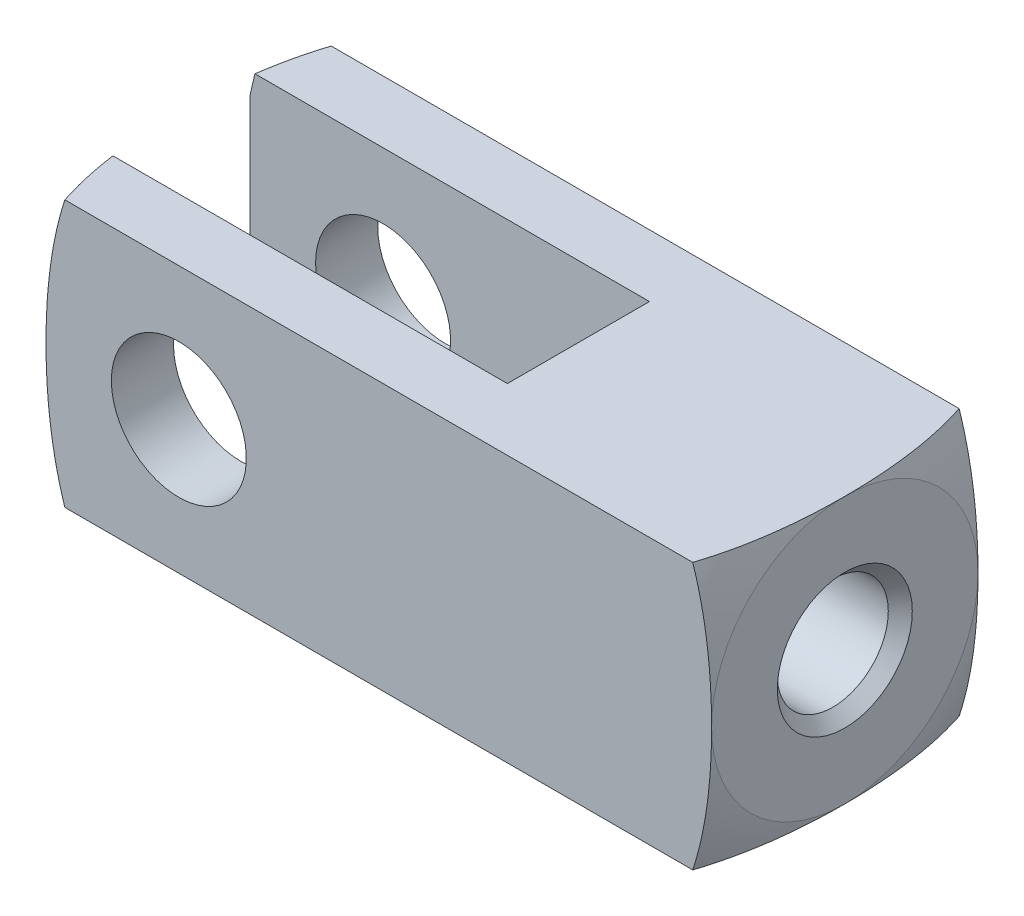
SolidWorks part; units mm, degrees
material "Plain Carbon Steel"
ref_plane "Front Plane" through (0, 0, 0) normal (0, 0, 1) x (1, 0, 0)
ref_plane "Top Plane" through (0, 0, 0) normal (0, 1, 0) x (1, 0, 0)
ref_plane "Right Plane" through (0, 0, 0) normal (1, 0, 0) x (0, 0, -1)
sketch "Sketch1" plane through (0, 0, 0) normal (0, 0, 1) x (1, 0, 0)
  line L0 (-4.7498, 4.7625) -> (-4.7498, -4.7625)
  line L1 (-4.7498, -4.7625) -> (19.05, -4.7625)
  line L2 (19.05, -4.7625) -> (19.05, 4.7625)
  line L3 (19.05, 4.7625) -> (-4.7498, 4.7625)
extrude "Boss-Extrude1" add sketch "Sketch1" against normal blind 4.7625 and the other way blind 4.7625
sketch "Sketch2" plane through (0, 0, 0) normal (0, 1, 0) x (1, 0, 0)
  line L0 (-4.7498, 2.54) -> (-4.7498, -2.54)
  line L1 (-4.7498, -2.54) -> (9.525, -2.54)
  line L2 (9.525, -2.54) -> (9.525, 2.54)
  line L3 (9.525, 2.54) -> (-4.7498, 2.54)
extrude "Cut-Extrude1" cut sketch "Sketch2" along normal blind 4.7625 and the other way blind 4.7625
hole_wizard "Hole1" positions "Sketch4" profile "Sketch3" legacy
sketch "Sketch4" plane through (19.05, 0, 0) normal (1, 0, 0) x (0, 0, -1)
  point P0 (0, 0)
sketch "Sketch3" plane through (19.05, 0, 0) normal (0, 1, 0) x (0, 0, -1)
  line L0 (0, 0) -> (0, 7.874)
  line L1 (0, 7.874) -> (1.9837, 7.874)
  line L2 (1.9837, 7.874) -> (1.9837, 0.4293)
  line L3 (1.9837, 0.4293) -> (2.413, 0)
  line L4 (2.413, 0) -> (0, 0)
  line L5 (0, -6.4453) -> (0, 115.525) construction
  line L6 (-1.9837, 0.4293) -> (-2.413, 0) construction
  dimension "Diameter" = 3.9675
  dimension "Depth" = 7.874
  dimension "C-Sink Angle" = 90
  dimension "C-Sink Diameter" = 4.826
cosmetic thread "Cosmetic Thread1" parameters "D1"=7.874, "D2"=4.826
ref_plane "Plane1" through (0, 0, 6.35) normal (0, 0, 1) x (1, 0, 0)
ref_plane "Plane2" through (0, 0, -6.35) normal (0, 0, 1) x (1, 0, 0)
ref_plane "Plane3" through (23.876, 0, 0) normal (1, 0, 0) x (0, 0, -1)
hole_wizard "Hole2" positions "Sketch6" profile "Sketch5" legacy
sketch "Sketch6" plane through (11.176, 0, 0) normal (1, 0, 0) x (0, 0, -1)
  point P0 (0, 0)
sketch "Sketch5" plane through (11.176, 0, 0) normal (0, 1, 0) x (0, 0, -1)
  line L0 (0, 0) -> (0, 1.651)
  line L1 (0, 1.651) -> (1.9837, 1.651)
  line L2 (1.9837, 1.651) -> (1.9837, 0)
  line L3 (1.9837, 0) -> (0, 0)
  line L4 (0, 110) -> (0, -10) construction
  dimension "Diameter" = 3.9675
  dimension "Depth" = 1.651
hole_wizard "Hole3" positions "Sketch8" profile "Sketch7" legacy
sketch "Sketch8" plane through (0, 0, -4.7625) normal (0, 0, -1) x (-1, 0, 0)
  point P0 (0, 0)
sketch "Sketch7" plane through (0, 0, -4.7625) normal (1, 0, 0) x (0, 1, 0)
  line L0 (0, 0) -> (0, 9.525)
  line L1 (0, 9.525) -> (2.413, 9.525)
  line L2 (2.413, 9.525) -> (2.413, 0)
  line L3 (2.413, 0) -> (0, 0)
  line L4 (0, 110) -> (0, -10) construction
  dimension "Diameter" = 4.826
  dimension "Depth" = 9.525
sketch "Sketch9" plane through (0, 0, 0) normal (0, 0, 1) x (1, 0, 0)
  line L0 (19.05, 0) -> (19.05, 4.7625)
  line L1 (16.51, 9.525) -> (23.8125, 9.525)
  line L2 (23.8125, 9.525) -> (23.8125, 0)
  line L3 (23.8125, 0) -> (19.05, 0)
  line L4 (23.8125, 0) -> (19.05, 0) construction
  arc A0 (19.05, 4.7625) -> (16.51, 9.525) centre (8.8503, 2.3812) ccw
revolve "Cut-Revolve1" cut sketch "Sketch9" angle 360 about L4 reverse direction yes
sketch "Sketch10" plane through (0, 0, 0) normal (0, 0, 1) x (1, 0, 0)
  line L0 (-9.5123, 0) -> (-9.5123, 9.525)
  line L1 (-9.5123, 9.525) -> (-2.2098, 9.525)
  line L2 (-4.7498, 4.7625) -> (-4.7498, 0)
  line L3 (-4.7498, 0) -> (-9.5123, 0)
  line L4 (-4.7498, 0) -> (-9.5123, 0) construction
  arc A0 (-2.2098, 9.525) -> (-4.7498, 4.7625) centre (5.4499, 2.3813) ccw
revolve "Cut-Revolve2" cut sketch "Sketch10" angle 360 about L4 reverse direction yes
ref_plane "Plane4" through (19.05, 0, 0) normal (1, 0, 0) x (0, 0, -1)
ref_plane "Plane5" through (9.525, 0, 0) normal (1, 0, 0) x (0, 0, -1)
ref_plane "dummy XY" through (0, 0, 0) normal (0, 0, 1) x (1, 0, 0)
ref_plane "dummy XZ" through (0, 0, 0) normal (0, -1, 0) x (-1, 0, 0)
ref_plane "dummy YZ" through (0, 0, 0) normal (1, 0, 0) x (0, 0, -1)
ref_axis "dummy X" through (-80.9, 0, 0) along (1, 0, 0)
ref_axis "dummy Y" through (0, -50, 0) along (0, 1, 0)
ref_axis "dummy Z" through (0, 0, 80.9) along (0, 0, -1)
sketch3d "dummy"
  point P0 (0, 0, 0)
ref_plane "h1 XY" through (0, 0, 0) normal (0, 0, 1) x (1, 0, 0)
ref_plane "h1 XZ" through (0, 4.7625, 0) normal (0, -1, 0) x (-1, 0, 0)
ref_plane "h1 YZ" through (-4.7498, 0, 0) normal (1, 0, 0) x (0, 0, -1)
ref_axis "h1 X" through (-80.9, 4.7625, 0) along (1, 0, 0)
ref_axis "h1 Y" through (-4.7498, -50, 0) along (0, 1, 0)
ref_axis "h1 Z" through (-4.7498, 4.7625, 80.9) along (0, 0, -1)
sketch3d "h1"
  point P0 (-4.7498, 4.7625, 0)
ref_plane "h2 XY" through (0, 0, 0) normal (0, 0, 1) x (1, 0, 0)
ref_plane "h2 XZ" through (0, -4.7625, 0) normal (0, -1, 0) x (-1, 0, 0)
ref_plane "h2 YZ" through (-4.7498, 0, 0) normal (1, 0, 0) x (0, 0, -1)
ref_axis "h2 X" through (-80.9, -4.7625, 0) along (1, 0, 0)
ref_axis "h2 Y" through (-4.7498, -50, 0) along (0, 1, 0)
ref_axis "h2 Z" through (-4.7498, -4.7625, 80.9) along (0, 0, -1)
sketch3d "h2"
  point P0 (-4.7498, -4.7625, 0)
ref_plane "l1 XY" through (0, 0, 0) normal (0, 0, 1) x (1, 0, 0)
ref_plane "l1 XZ" through (0, 4.7625, 0) normal (0, -1, 0) x (-1, 0, 0)
ref_plane "l1 YZ" through (19.05, 0, 0) normal (1, 0, 0) x (0, 0, -1)
ref_axis "l1 X" through (-80.9, 4.7625, 0) along (1, 0, 0)
ref_axis "l1 Y" through (19.05, -50, 0) along (0, 1, 0)
ref_axis "l1 Z" through (19.05, 4.7625, 80.9) along (0, 0, -1)
sketch3d "l1"
  point P0 (19.05, 4.7625, 0)
ref_plane "l11 XY" through (0, 0, 0) normal (0, 0, 1) x (1, 0, 0)
ref_plane "l11 XZ" through (0, 4.7625, 0) normal (0, -1, 0) x (-1, 0, 0)
ref_plane "l11 YZ" through (19.05, 0, 0) normal (1, 0, 0) x (0, 0, -1)
ref_axis "l11 X" through (-80.9, 4.7625, 0) along (1, 0, 0)
ref_axis "l11 Y" through (19.05, -50, 0) along (0, 1, 0)
ref_axis "l11 Z" through (19.05, 4.7625, 80.9) along (0, 0, -1)
sketch3d "l11"
  point P0 (19.05, 4.7625, 0)
ref_plane "l12 XY" through (0, 0, 0) normal (0, 0, 1) x (1, 0, 0)
ref_plane "l12 XZ" through (0, 4.7625, 0) normal (0, -1, 0) x (-1, 0, 0)
ref_plane "l12 YZ" through (0, 0, 0) normal (1, 0, 0) x (0, 0, -1)
ref_axis "l12 X" through (-80.9, 4.7625, 0) along (1, 0, 0)
ref_axis "l12 Y" through (0, -50, 0) along (0, 1, 0)
ref_axis "l12 Z" through (0, 4.7625, 80.9) along (0, 0, -1)
sketch3d "l12"
  point P0 (0, 4.7625, 0)
ref_plane "l2 XY" through (0, 0, 0) normal (0, 0, 1) x (1, 0, 0)
ref_plane "l2 XZ" through (0, 4.7625, 0) normal (0, -1, 0) x (-1, 0, 0)
ref_plane "l2 YZ" through (-4.7498, 0, 0) normal (1, 0, 0) x (0, 0, -1)
ref_axis "l2 X" through (-80.9, 4.7625, 0) along (1, 0, 0)
ref_axis "l2 Y" through (-4.7498, -50, 0) along (0, 1, 0)
ref_axis "l2 Z" through (-4.7498, 4.7625, 80.9) along (0, 0, -1)
sketch3d "l2"
  point P0 (-4.7498, 4.7625, 0)
ref_plane "l21 XY" through (0, 0, 0) normal (0, 1, 0) x (1, 0, 0)
ref_plane "l21 XZ" through (0, 0, 0) normal (0, 0, 1) x (1, 0, 0)
ref_plane "l21 YZ" through (19.05, 0, 0) normal (1, 0, 0) x (0, 0, -1)
ref_axis "l21 X" through (-80.9, 0, 0) along (1, 0, 0)
ref_axis "l21 Y" through (19.05, 0, 50) along (0, 0, -1)
ref_axis "l21 Z" through (19.05, 50, 0) along (0, -1, 0)
sketch3d "l21"
  point P0 (19.05, 0, 0)
ref_plane "l22 XY" through (0, 0, 0) normal (0, 1, 0) x (1, 0, 0)
ref_plane "l22 XZ" through (0, 0, 0) normal (0, 0, 1) x (1, 0, 0)
ref_plane "l22 YZ" through (9.525, 0, 0) normal (1, 0, 0) x (0, 0, -1)
ref_axis "l22 X" through (-80.9, 0, 0) along (1, 0, 0)
ref_axis "l22 Y" through (9.525, 0, 50) along (0, 0, -1)
ref_axis "l22 Z" through (9.525, 50, 0) along (0, -1, 0)
sketch3d "l22"
  point P0 (9.525, 0, 0)
ref_plane "piston_rod_clevis XY" through (19.05, 0, 0) normal (1, 0, 0) x (0, 0, -1)
ref_plane "piston_rod_clevis XZ" through (0, 0, 0) normal (0, -1, 0) x (-1, 0, 0)
ref_plane "piston_rod_clevis YZ" through (0, 0, 0) normal (0, 0, -1) x (-1, 0, 0)
ref_axis "piston_rod_clevis X" through (19.05, 0, 80.9) along (0, 0, -1)
ref_axis "piston_rod_clevis Y" through (19.05, -50, 0) along (0, 1, 0)
ref_axis "piston_rod_clevis Z" through (80.9, 0, 0) along (-1, 0, 0)
sketch3d "piston_rod_clevis"
  point P0 (19.05, 0, 0)
ref_plane "rod_clevis_body XY" through (0, 0, 0) normal (0, 0, 1) x (1, 0, 0)
ref_plane "rod_clevis_body XZ" through (0, 0, 0) normal (0, -1, 0) x (-1, 0, 0)
ref_plane "rod_clevis_body YZ" through (0, 0, 0) normal (1, 0, 0) x (0, 0, -1)
ref_axis "rod_clevis_body X" through (-80.9, 0, 0) along (1, 0, 0)
ref_axis "rod_clevis_body Y" through (0, -50, 0) along (0, 1, 0)
ref_axis "rod_clevis_body Z" through (0, 0, 80.9) along (0, 0, -1)
sketch3d "rod_clevis_body"
  point P0 (0, 0, 0)
ref_plane "th1 XY" through (0, 0, 0) normal (0, 0, 1) x (1, 0, 0)
ref_plane "th1 XZ" through (0, 2.413, 0) normal (0, -1, 0) x (-1, 0, 0)
ref_plane "th1 YZ" through (19.05, 0, 0) normal (1, 0, 0) x (0, 0, -1)
ref_axis "th1 X" through (-80.9, 2.413, 0) along (1, 0, 0)
ref_axis "th1 Y" through (19.05, -50, 0) along (0, 1, 0)
ref_axis "th1 Z" through (19.05, 2.413, 80.9) along (0, 0, -1)
sketch3d "th1"
  point P0 (19.05, 2.413, 0)
ref_plane "th2 XY" through (0, 0, 0) normal (0, 0, 1) x (1, 0, 0)
ref_plane "th2 XZ" through (0, -2.413, 0) normal (0, -1, 0) x (-1, 0, 0)
ref_plane "th2 YZ" through (19.05, 0, 0) normal (1, 0, 0) x (0, 0, -1)
ref_axis "th2 X" through (-80.9, -2.413, 0) along (1, 0, 0)
ref_axis "th2 Y" through (19.05, -50, 0) along (0, 1, 0)
ref_axis "th2 Z" through (19.05, -2.413, 80.9) along (0, 0, -1)
sketch3d "th2"
  point P0 (19.05, -2.413, 0)
ref_plane "to_cylinder XY" through (9.525, 0, 0) normal (1, 0, 0) x (0, 0, -1)
ref_plane "to_cylinder XZ" through (0, 0, 0) normal (0, -1, 0) x (-1, 0, 0)
ref_plane "to_cylinder YZ" through (0, 0, 0) normal (0, 0, -1) x (-1, 0, 0)
ref_axis "to_cylinder X" through (9.525, 0, 80.9) along (0, 0, -1)
ref_axis "to_cylinder Y" through (9.525, -50, 0) along (0, 1, 0)
ref_axis "to_cylinder Z" through (80.9, 0, 0) along (-1, 0, 0)
sketch3d "to_cylinder"
  point P0 (9.525, 0, 0)
ref_plane "w1 XY" through (0, 0, 0) normal (0, 1, 0) x (1, 0, 0)
ref_plane "w1 XZ" through (0, 0, -4.7625) normal (0, 0, 1) x (1, 0, 0)
ref_plane "w1 YZ" through (19.05, 0, 0) normal (1, 0, 0) x (0, 0, -1)
ref_axis "w1 X" through (-80.9, 0, -4.7625) along (1, 0, 0)
ref_axis "w1 Y" through (19.05, 0, 50) along (0, 0, -1)
ref_axis "w1 Z" through (19.05, 50, -4.7625) along (0, -1, 0)
sketch3d "w1"
  point P0 (19.05, 0, -4.7625)
ref_plane "w11 XY" through (0, 0, 0) normal (0, 1, 0) x (1, 0, 0)
ref_plane "w11 XZ" through (0, 0, -2.54) normal (0, 0, 1) x (1, 0, 0)
ref_plane "w11 YZ" through (-4.7498, 0, 0) normal (1, 0, 0) x (0, 0, -1)
ref_axis "w11 X" through (-80.9, 0, -2.54) along (1, 0, 0)
ref_axis "w11 Y" through (-4.7498, 0, 50) along (0, 0, -1)
ref_axis "w11 Z" through (-4.7498, 50, -2.54) along (0, -1, 0)
sketch3d "w11"
  point P0 (-4.7498, 0, -2.54)
ref_plane "w12 XY" through (0, 0, 0) normal (0, 1, 0) x (1, 0, 0)
ref_plane "w12 XZ" through (0, 0, 2.54) normal (0, 0, 1) x (1, 0, 0)
ref_plane "w12 YZ" through (-4.7498, 0, 0) normal (1, 0, 0) x (0, 0, -1)
ref_axis "w12 X" through (-80.9, 0, 2.54) along (1, 0, 0)
ref_axis "w12 Y" through (-4.7498, 0, 50) along (0, 0, -1)
ref_axis "w12 Z" through (-4.7498, 50, 2.54) along (0, -1, 0)
sketch3d "w12"
  point P0 (-4.7498, 0, 2.54)
ref_plane "w2 XY" through (0, 0, 0) normal (0, 1, 0) x (1, 0, 0)
ref_plane "w2 XZ" through (0, 0, 4.7625) normal (0, 0, 1) x (1, 0, 0)
ref_plane "w2 YZ" through (19.05, 0, 0) normal (1, 0, 0) x (0, 0, -1)
ref_axis "w2 X" through (-80.9, 0, 4.7625) along (1, 0, 0)
ref_axis "w2 Y" through (19.05, 0, 50) along (0, 0, -1)
ref_axis "w2 Z" through (19.05, 50, 4.7625) along (0, -1, 0)
sketch3d "w2"
  point P0 (19.05, 0, 4.7625)
